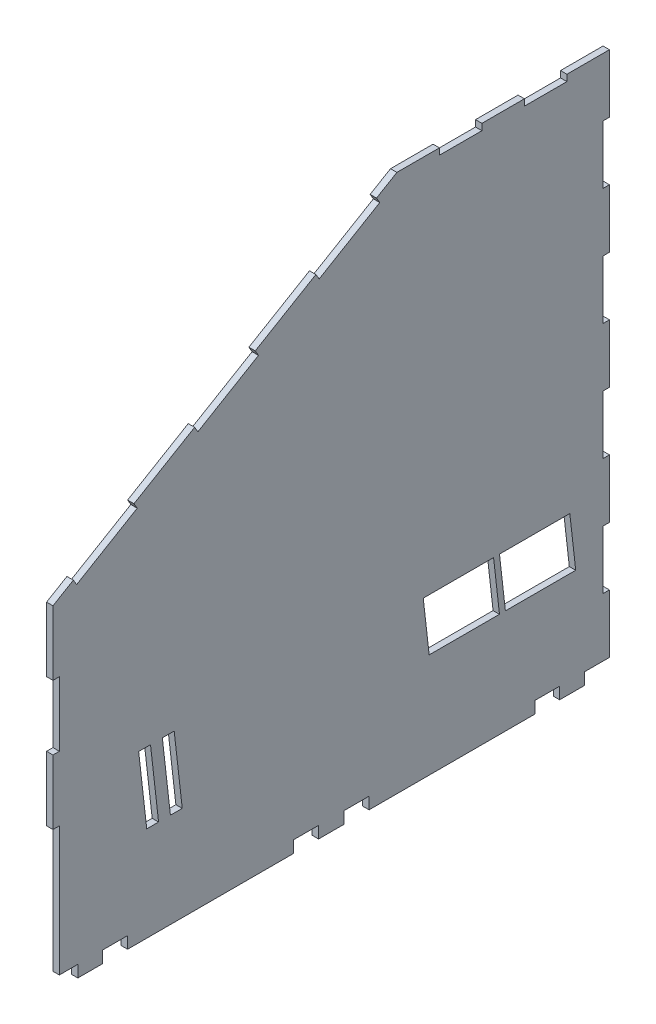
SolidWorks part; units mm, degrees
ref_plane "Ön Düzlem" through (0, 0, 0) normal (0, 0, 1) x (1, 0, 0)
ref_plane "Üst Düzlem" through (0, 0, 0) normal (0, 1, 0) x (1, 0, 0)
ref_plane "Sağ Düzlem" through (0, 0, 0) normal (1, 0, 0) x (0, 0, -1)
sketch "Sketch1" plane through (0, 0, 0) normal (1, 0, 0) x (0, 0, -1)
  line L0 (117.52, 112.5) -> (99.566, 112.5)
  line L6 (117.52, -109.8) -> (117.52, -85.1)
  line L13 (-107.0133, -112.5) -> (-107.0133, -114.8)
  line L14 (-6.4686, 92.2661) -> (-32.0795, 77.122)
  line L17 (27.75, 112.5) -> (19.1423, 107.4101)
  line L18 (-114.82, -109.8) -> (-107.0133, -109.8)
  line L20 (-107.0133, -114.8) -> (-96.5067, -114.8)
  line L21 (-86, -112.5) -> (-86, -114.8)
  line L22 (-114.82, -27.96) -> (-114.82, -0.68)
  line L23 (-117.52, -55.24) -> (-117.52, -27.96)
  line L24 (-96.5067, -114.8) -> (-96.5067, -112.5)
  line L25 (-117.52, -0.68) -> (-117.52, 26.6)
  line L26 (-117.52, -0.68) -> (-114.82, -0.68)
  line L27 (-117.52, -27.96) -> (-114.82, -27.96)
  line L28 (-114.82, -82.52) -> (-114.82, -55.24)
  line L29 (-117.52, -55.24) -> (-114.82, -55.24)
  line L31 (-86, -109.8) -> (-86, -112.5)
  line L32 (-107.0133, -109.8) -> (-107.0133, -112.5)
  line L33 (-96.5067, -109.8) -> (-96.5067, -112.5)
  line L34 (-96.5067, -109.8) -> (-86, -109.8)
  line L35 (-5.3333, -112.5) -> (-5.3333, -114.8)
  line L37 (-16, -112.5) -> (-16, -109.8)
  line L38 (-16, -109.8) -> (-5.3333, -109.8)
  line L39 (-5.3333, -114.8) -> (5.3333, -114.8)
  line L40 (-86, -114.8) -> (-16, -114.8)
  line L41 (5.3333, -109.8) -> (16, -109.8)
  line L42 (-5.3333, -109.8) -> (-5.3333, -112.5)
  line L43 (5.3333, -109.8) -> (5.3333, -112.5)
  line L44 (16, -109.8) -> (16, -112.5)
  line L45 (5.3333, -114.8) -> (5.3333, -112.5)
  line L46 (96.5067, -112.5) -> (96.5067, -114.8)
  line L47 (114.82, -35.7) -> (114.82, -11)
  line L48 (86, -109.8) -> (96.5067, -109.8)
  line L49 (96.5067, -114.8) -> (107.0133, -114.8)
  line L51 (86, -109.8) -> (86, -112.5)
  line L52 (96.5067, -109.8) -> (96.5067, -112.5)
  line L53 (107.0133, -109.8) -> (107.0133, -112.5)
  line L55 (107.0133, -109.8) -> (117.52, -109.8)
  line L56 (117.52, -60.4) -> (117.52, -35.7)
  line L57 (114.82, 13.7) -> (114.82, 38.4)
  line L58 (117.52, -11) -> (117.52, 13.7)
  line L59 (114.82, 63.1) -> (114.82, 87.8)
  line L60 (117.52, 38.4) -> (117.52, 63.1)
  line L61 (107.0133, -112.5) -> (107.0133, -114.8)
  line L62 (117.52, 87.8) -> (117.52, 112.5)
  line L63 (114.82, -85.1) -> (114.82, -60.4)
  line L64 (117.52, -85.1) -> (114.82, -85.1)
  line L65 (117.52, 13.7) -> (114.82, 13.7)
  line L66 (117.52, 87.8) -> (114.82, 87.8)
  line L67 (117.52, 63.1) -> (114.82, 63.1)
  line L68 (117.52, 38.4) -> (114.82, 38.4)
  line L69 (117.52, -11) -> (114.82, -11)
  line L70 (117.52, -35.7) -> (114.82, -35.7)
  line L71 (117.52, -60.4) -> (114.82, -60.4)
  line L72 (-57.6905, 61.978) -> (-83.3014, 46.8339)
  line L73 (-5.0944, 89.942) -> (-6.4686, 92.2661)
  line L74 (-107.538, 29.3658) -> (-81.9271, 44.5098)
  line L75 (-16, -114.8) -> (-16, -112.5)
  line L76 (99.566, 109.8) -> (81.612, 109.8)
  line L77 (16, -112.5) -> (16, -114.8)
  line L78 (63.658, 109.8) -> (45.704, 109.8)
  line L79 (-108.9123, 31.6899) -> (-117.52, 26.6)
  line L80 (45.704, 109.8) -> (45.704, 112.5)
  line L81 (63.658, 109.8) -> (63.658, 112.5)
  line L82 (81.612, 109.8) -> (81.612, 112.5)
  line L83 (99.566, 109.8) -> (99.566, 112.5)
  line L84 (16, -114.8) -> (86, -114.8)
  line L85 (86, -114.8) -> (86, -112.5)
  line L87 (-108.9123, 31.6899) -> (-107.538, 29.3658)
  line L88 (19.1423, 107.4101) -> (20.5165, 105.086)
  line L89 (-56.3162, 59.6539) -> (-30.7053, 74.7979)
  line L91 (-5.0944, 89.942) -> (20.5165, 105.086)
  line L92 (-30.7053, 74.7979) -> (-32.0795, 77.122)
  line L93 (-56.3162, 59.6539) -> (-57.6905, 61.978)
  line L94 (-81.9271, 44.5098) -> (-83.3014, 46.8339)
  line L95 (45.704, 112.5) -> (27.75, 112.5)
  line L97 (81.612, 112.5) -> (63.658, 112.5)
  line L98 (-114.82, -82.52) -> (-114.82, -109.8)
  line L103 (-77.9109, -74.8) -> (-72.9109, -74.8)
  line L114 (-62.9109, -74.8) -> (-67.9109, -74.8)
  line L209 (100.78, -48.8) -> (71.08, -48.8)
  line L211 (100.78, -70.8) -> (73.58, -70.8)
  line L212 (68.58, -48.8) -> (71.08, -70.8)
  line L215 (71.08, -48.8) -> (73.58, -70.8)
  line L216 (41.38, -48.8) -> (38.88, -48.8)
  line L217 (38.88, -48.8) -> (41.38, -70.8)
  line L218 (100.78, -70.8) -> (103.28, -70.8)
  line L219 (100.78, -48.8) -> (103.28, -70.8)
  line L220 (71.08, -70.8) -> (41.38, -70.8)
  line L221 (68.58, -48.8) -> (41.38, -48.8)
  line L223 (-76.32, -44.8) -> (-81.32, -44.8)
  line L225 (-77.9109, -74.8) -> (-81.32, -44.8)
  line L226 (-72.9109, -74.8) -> (-76.32, -44.8)
  line L227 (-67.9109, -74.8) -> (-71.32, -44.8)
  line L228 (-62.9109, -74.8) -> (-66.32, -44.8)
  line L229 (-71.32, -44.8) -> (-66.32, -44.8)
  point P0 (0, 0)
  dimension "D1" = 3
extrude "Boss-Extrude1" add sketch "Sketch1" along normal blind 2.7 contours L82 L97 L81 L78 L80 L95 L17 L88 L91 L73 L14 L92 L89 L93 L72 L94 L74 L87 L79 L25 L26 L22 L27 L23 L29 L28 L18 L32 L33 L34 L31 L37 L38 L42 L43 L41 L44 L51 L48 L52 L53 region at (0, -10.5197, -8.06)
ref_plane "Plane1" through (2.7, 112.5, -27.75) normal (0, -0.509, 0.8608) x (1, 0, 0)
